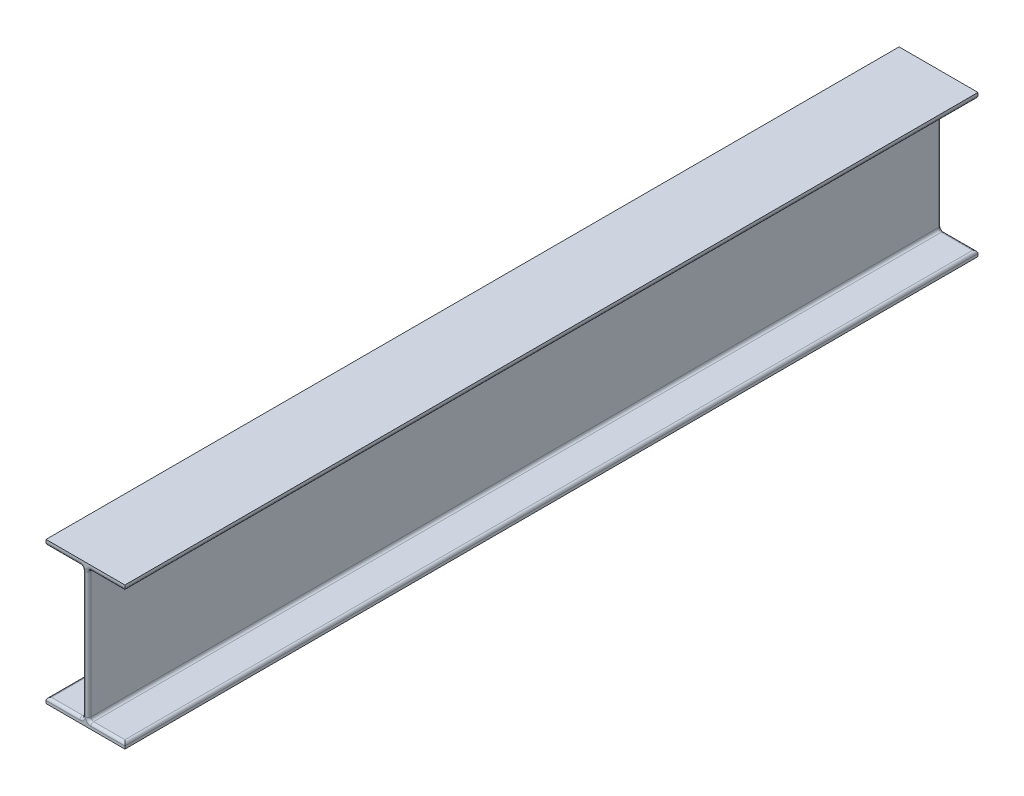
SolidWorks part; units mm, degrees
ref_plane "Front" through (0, 0, 0) normal (0, 0, 1) x (1, 0, 0)
ref_plane "Top" through (0, 0, 0) normal (0, 1, 0) x (1, 0, 0)
ref_plane "Right" through (0, 0, 0) normal (1, 0, 0) x (0, 0, -1)
sketch "Sketch1" plane through (0, 0, 0) normal (0, 0, 1) x (1, 0, 0)
  line L0 (42.291, 152.4) -> (-42.291, 152.4)
  line L1 (-42.291, 152.4) -> (-42.291, 146.558)
  line L2 (-42.291, 146.558) -> (-2.921, 146.558)
  line L3 (-2.921, 146.558) -> (-2.921, 5.842)
  line L4 (-2.921, 5.842) -> (-42.291, 5.842)
  line L5 (-42.291, 5.842) -> (-42.291, 0)
  line L6 (-42.291, 0) -> (42.291, 0)
  line L7 (42.291, 0) -> (42.291, 5.842)
  line L8 (42.291, 5.842) -> (2.921, 5.842)
  line L9 (2.921, 5.842) -> (2.921, 146.558)
  line L10 (2.921, 146.558) -> (42.291, 146.558)
  line L11 (42.291, 146.558) -> (42.291, 152.4)
  dimension "D1" = 5.842
  dimension "Thickness" = 5.842
  dimension "Width" = 84.582
  dimension "Height" = 152.4
extrude "Boss-Extrude1" add sketch "Sketch1" along normal mid plane 914.4
fillet "Fillet1" radius 2.921 20 edges at (42.291, 5.842, 0) (-42.291, 146.558, 0) (42.291, 146.558, 0) (-42.291, 5.842, 0) (-22.606, 146.558, 457.2) (22.606, 146.558, 457.2) (22.606, 5.842, 457.2) (2.921, 76.2, 457.2) (-22.606, 5.842, 457.2) (-2.921, 76.2, 457.2) (-22.606, 146.558, -457.2) (-22.606, 5.842, -457.2) (-2.921, 146.558, 0) (-2.921, 5.842, 0) (-2.921, 76.2, -457.2) (22.606, 146.558, -457.2) (22.606, 5.842, -457.2) (2.921, 5.842, 0) (2.921, 146.558, 0) (2.921, 76.2, -457.2)
equation "\"D1@Sketch1\" = \"Thickness@Sketch1\""
equation "\"D1@Fillet1\" = \"Thickness@Sketch1\"/2"
